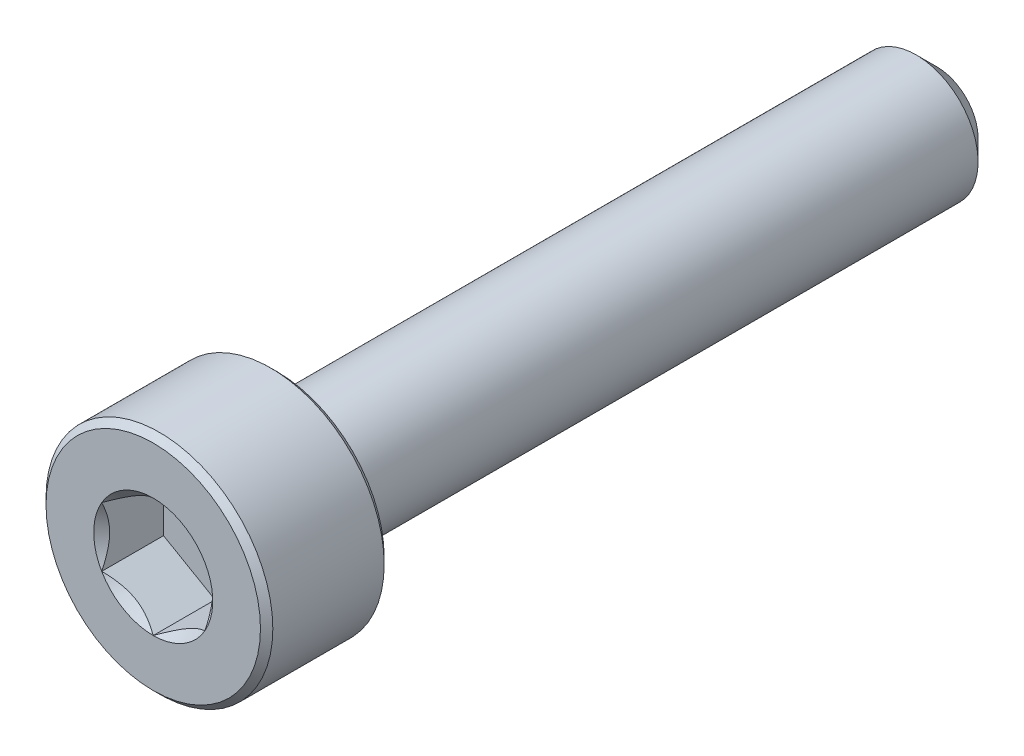
SolidWorks part; units mm, degrees
ref_plane "Front Plane" through (0, 0, 0) normal (0, 0, 1) x (1, 0, 0)
ref_plane "Top Plane" through (0, 0, 0) normal (0, 1, 0) x (1, 0, 0)
ref_plane "Right Plane" through (0, 0, 0) normal (1, 0, 0) x (0, 0, -1)
sketch "Sketch1" plane through (0, 0, 0) normal (1, 0, 0) x (0, 0, -1)
  line L0 (-9.5, 0) -> (9.5, 0) construction
  line L1 (9.5, 0) -> (9.5, 1) construction
  line L2 (9.5, 1) -> (9, 1.5) construction
  line L3 (9, 1.5) -> (-6.5, 1.5) construction
  line L5 (-6.5, 1.5) -> (-6.5, 2.75) construction
  line L6 (-6.5, 2.75) -> (-9.5, 2.75) construction
  line L7 (-9.5, 2.75) -> (-9.5, 0) construction
  line L8 (9.5, 1) -> (9.5, 1.5) construction
  line L9 (9.4688, 1.5541) -> (9.7188, 1.1211) construction
  line L10 (9.7188, 1.1211) -> (9.9688, 1.5541) construction
  line L11 (9.9688, 1.5541) -> (9.4688, 1.5541) construction
  line L12 (9.7188, 1.5541) -> (9.7188, 1.5) construction
  line L13 (9.7188, 1.1211) -> (9.7188, 1.1752) construction
  line L14 (9.6875, 1.1752) -> (9.75, 1.1752) construction
  line L15 (9.5, 1.5) -> (9.9375, 1.5) construction
  line L16 (9.4844, 1.5271) -> (9.9531, 1.5271) construction
  line L17 (9.5, 0) -> (9.5, -1.5) construction
  line L18 (-6.65, 2.75) -> (-6.5, 2.6) construction
  line L19 (-9.35, 2.75) -> (-9.5, 2.6) construction
  point P0 (-9.5, 1.25)
  point P3 (7.75, 1.5)
  point P4 (0, 0)
  point P22 (9.7188, 1.1752)
  point P24 (-6.5, 1.5)
  point P25 (9.7188, 1.5)
  point P28 (9.7188, 1.5271)
  point P29 (7.75, -1.5)
  point P31 (-8, 2.75)
  point P37 (-7.025, 2.75)
  point P38 (-9.275, 2.75)
  point P41 (-8, 0)
  dimension "head height" = 3
  dimension "D1" = 45
  dimension "Head Diameter" = 5.5
  dimension "Thread Size" = 3
  dimension "drive size" = 2.5
  dimension "Thread Pitch" = 0.5
  dimension "D2" = 0.0625
  dimension "D3" = 0.5
  dimension "D4" = 1.75
  dimension "D7" = 0.15
  dimension "D8" = 0.15
  dimension "D9" = 0.15
  dimension "D10" = 0.075
  dimension "D11" = 0.375
  dimension "length" = 16
  dimension "Drive Depth" = 1.5
sketch "Sketch2" plane through (0, 0, 0) normal (1, 0, 0) x (0, 0, -1)
  line L1 (-9.35, 2.75) -> (-6.65, 2.75)
  line L4 (9, 1.5) -> (9.5, 1)
  line L5 (9.5, 1) -> (9.5, 0)
  line L6 (-6.65, 2.75) -> (-6.5, 2.6) construction
  line L7 (9.5, 0) -> (-9.5, 0)
  line L8 (-9.35, 2.75) -> (-9.5, 2.6) construction
  line L9 (-6.65, 2.75) -> (-6.5, 2.6)
  line L10 (-9.35, 2.75) -> (-9.5, 2.6)
  line L11 (-9.5, 2.6) -> (-9.5, 0)
  line L12 (-6.5, 2.6) -> (-6.5, 1.5)
  line L13 (-6.5, 1.5) -> (9, 1.5)
revolve "Revolve1" add sketch "Sketch2" angle 360 about L7
sketch "Sketch3" plane through (0, 0, 9.5) normal (0, 0, 1) x (1, 0, 0)
  line L1 (0, 1.4434) -> (-1.25, 0.7217)
  line L2 (-1.25, 0.7217) -> (-1.25, -0.7217)
  line L3 (-1.25, -0.7217) -> (0, -1.4434)
  line L4 (0, -1.4434) -> (1.25, -0.7217)
  line L5 (1.25, -0.7217) -> (1.25, 0.7217)
  line L6 (1.25, 0.7217) -> (0, 1.4434)
  circle A0 centre (0, 0) radius 1.25 construction
  dimension "D1" = 2.5
extrude "Cut-Extrude1" cut sketch "Sketch3" against normal up to vertex (1.5 mm away) up to point (0, 0, 8)
sketch "Sketch4" plane through (0, 0, 9.5) normal (0, 0, 1) x (1, 0, 0)
  circle A0 centre (0, 0) radius 1.4434
extrude "Cut-Extrude2" cut sketch "Sketch4" against normal blind 0.5 draft 45
ref_plane "Plane1" [suppressed] through (0, 0, 6.5) normal (0, 0, 1) x (1, 0, 0)
split "Split1" [suppressed] bodies to split 106
sketch "Sketch6" [suppressed] plane through (0, 0, -9.5) normal (0, 0, -1) x (-1, 0, 0)
  circle A0 centre (0, 0) radius 1.5
curve "Helix/Spiral1" [suppressed] pitch 0.5 height 16.5 turns 33
sketch "Sketch7" [suppressed] plane through (0, 0, 0) normal (1, 0, 0) x (0, 0, -1)
  line L0 (9.4844, 1.5271) -> (9.9531, 1.5271)
  line L1 (9.9531, 1.5271) -> (9.75, 1.1752)
  line L2 (9.75, 1.1752) -> (9.6875, 1.1752)
  line L3 (9.6875, 1.1752) -> (9.4844, 1.5271)
sweep "Cut-Sweep1" [suppressed] cut profiles "Sketch7" path "Helix/Spiral1"
sketch "Sketch8" [suppressed] plane through (0, 0, 6.5) normal (0, 0, -1) x (-1, 0, 0)
  circle A0 centre (0, 0) radius 1.5
extrude "Boss-Extrude1" [suppressed] add sketch "Sketch8" along normal through all draft 45
ref_plane "Plane2" [suppressed] through (0, 0, 8) normal (0, 0, 1) x (1, 0, 0)
sketch "Sketch9" [suppressed] plane through (0, 0, 8) normal (0, 0, 1) x (1, 0, 0)
  line L0 (0, 2.6744) -> (0.072, 2.7491)
  line L1 (0, 2.6744) -> (-0.072, 2.7491)
  line L2 (0, 2.75) -> (0, 0) construction
  line L3 (-0.072, 2.7491) -> (0, 0) construction
  line L4 (0, 0) -> (0.072, 2.7491) construction
  arc A0 (0.072, 2.7491) -> (-0.072, 2.7491) centre (0, 0) ccw
  circle A1 centre (0, 0) radius 2.6744 construction
  dimension "D1" = 5.5
  dimension "D2" = 5.3487
  dimension "D3" = 3
extrude "Cut-Extrude4" [suppressed] cut sketch "Sketch9" against normal up to vertex and the other way up to vertex
pattern_circular "CirPattern2" [suppressed] count 96 over 360 about axis through (0, 0, 9.5) along (0, 0, -1) of bodies 113
equation "\"D2@Sketch1\" = \"Thread Pitch@Sketch1\" / 8"
equation "\"D3@Sketch1\" = \"Thread Pitch@Sketch1\""
equation "\"D3@Helix/Spiral1\" = \"length@Sketch1\" + \"Thread Pitch@Sketch1\""
equation "\"D4@Helix/Spiral1\" = \"Thread Pitch@Sketch1\""
equation "\"D4@Sketch1\" = \"Thread Pitch@Sketch1\" * 3.5"
equation "\"D7@Sketch1\"=\"head height@Sketch1\"*.05"
equation "\"D8@Sketch1\"=\"D7@Sketch1\""
equation "\"D9@Sketch1\"=\"D7@Sketch1\""
equation "\"D10@Sketch1\"=\"D7@Sketch1\"/2"
equation "\"D11@Sketch1\"=\"D10@Sketch1\"*5"
equation "\"D1@CirPattern2\"=( 360 / \"D3@Sketch9\" )*0.8"
equation "\"D1@Sketch3\" = \"drive size@Sketch1\""
equation "\"D2@Sketch9\"=\"Head Diameter@Sketch1\" * 0.9725"
